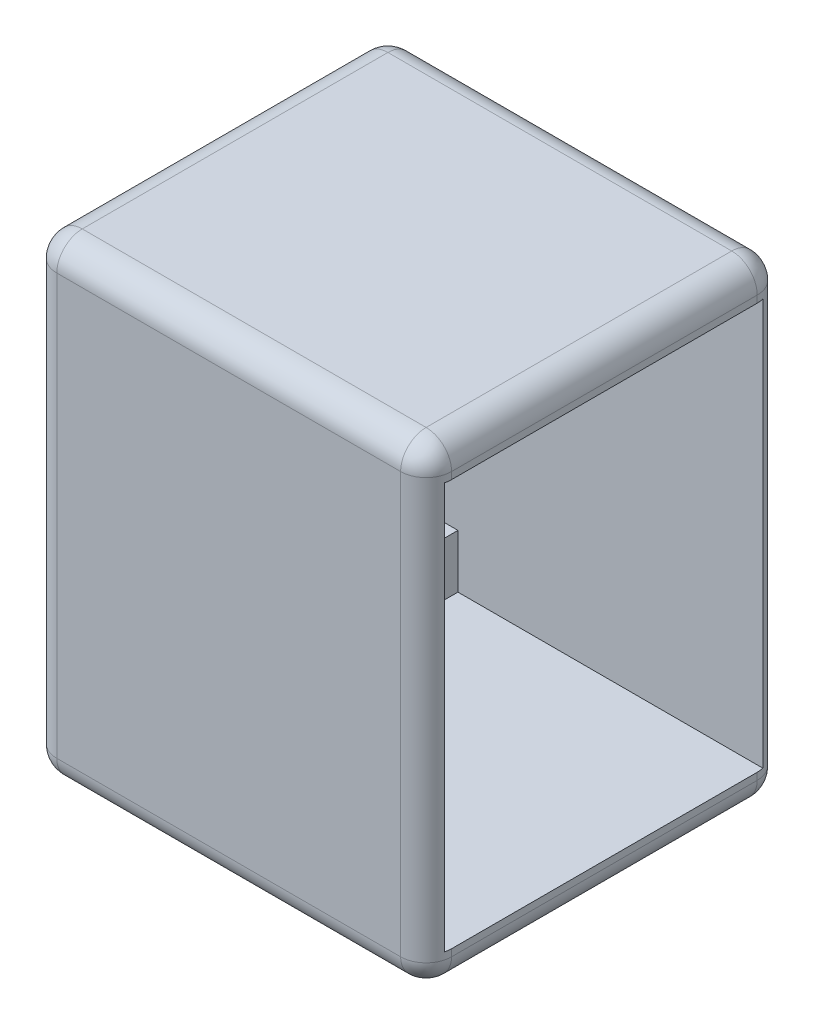
SolidWorks part; units mm, degrees
material "PLA"
ref_plane "Front Plane" through (0, 0, 0) normal (1, 0, 0) x (0, 1, 0)
ref_plane "Top Plane" through (0, 0, 0) normal (0, 0, 1) x (0, 1, 0)
ref_plane "Right Plane" through (0, 0, 0) normal (0, 1, 0) x (-1, 0, 0)
sketch "Sketch1" plane through (0, 0, 0) normal (1, 0, 0) x (0, 1, 0)
  line L5 (-37, 14) -> (-30.25, 14) construction
  line L6 (-37, 28) -> (0, 28)
  line L11 (-37, 28) -> (-37, 0)
  line L12 (-37, 0) -> (0, 0)
  line L20 (0, 28) -> (0, 0)
  line L21 (-30.25, 26.5) -> (-6.75, 26.5)
  line L22 (-30.25, 26.5) -> (-30.25, 1.5)
  line L23 (-30.25, 1.5) -> (-6.75, 1.5)
  line L24 (-6.75, 26.5) -> (-6.75, 1.5)
  line L25 (-6.75, 14) -> (0, 14) construction
  line L26 (-18.5, 0) -> (-18.5, 1.5) construction
  line L27 (-18.5, 28) -> (-18.5, 26.5) construction
  line L29 (-34.45, 1.5) -> (-2.55, 1.5)
  line L30 (-34.45, 1.5) -> (-34.45, 26.5)
  line L31 (-34.45, 26.5) -> (-2.55, 26.5)
  line L32 (-2.55, 1.5) -> (-2.55, 26.5)
  dimension "D1" = 4.2
  dimension "D2" = 25
  dimension "D3" = 4.2
  dimension "D6" = 37
  dimension "D7" = 23.5
  dimension "D9" = 1.5
extrude "Boss-Extrude1" add sketch "Sketch1" along normal blind 26 contours L20 L6 L11 L12 L21 L24 L23 L22 region at (0, -18.5, 27.536)
extrude "Boss-Extrude2" add sketch "Sketch1<3>" along normal blind 2 contours L31 L30 L29 L22 | L29 L32 L31 L24 region at (0, -32.35, 14) region at (0, -4.65, 14)
sketch "Sketch1<3>" plane through (0, 0, 0) normal (1, 0, 0) x (0, 1, 0) same geometry as "Sketch1"
sketch "Sketch2" plane through (26, 0, 0) normal (1, 0, 0) x (0, 1, 0)
  line L1 (-37, 28) -> (0, 28)
  line L2 (-37, 28) -> (-37, 0)
  line L3 (-37, 0) -> (0, 0)
  line L4 (0, 28) -> (0, 0)
sketch "Sketch3" plane through (0, 0, 0) normal (-1, 0, 0) x (0, -1, 0)
  line L1 (0, 28) -> (37, 28)
  line L2 (0, 28) -> (0, 0)
  line L3 (0, 0) -> (37, 0)
  line L4 (37, 28) -> (37, 0)
  line L5 (2.55, 26.5) -> (34.45, 26.5)
  line L6 (2.55, 26.5) -> (2.55, 1.5)
  line L7 (2.55, 1.5) -> (34.45, 1.5)
  line L8 (34.45, 26.5) -> (34.45, 1.5)
extrude "Boss-Extrude4" add sketch "Sketch3" along normal blind 3.5
sketch "Sketch5" plane through (-3.5, 0, 0) normal (-1, 0, 0) x (0, -1, 0)
  line L0 (23.25, 20) -> (23.25, 8) construction
  line L1 (0, 28) -> (37, 28)
  line L2 (0, 28) -> (0, 0)
  line L3 (0, 0) -> (37, 0)
  line L4 (37, 28) -> (37, 0)
  line L5 (30.25, 26.5) -> (30.25, 1.5) construction
  line L6 (34.45, 26.5) -> (2.55, 26.5) construction
  circle A0 centre (23.25, 20) radius 5.2
  circle A1 centre (23.25, 8) radius 5.2
  dimension "D1" = 10.4
  dimension "D2" = 7
  dimension "D3" = 12
  dimension "D4" = 6.5
extrude "Boss-Extrude5" add sketch "Sketch5" along normal blind 1.5
sketch "Sketch11" plane through (0, -37, 0) normal (0, -1, 0) x (1, 0, 0)
  line L0 (2.375, 14) -> (17.375, 14) construction
  line L1 (17.375, 10.4) -> (2.375, 11.65)
  line L2 (17.375, 17.6) -> (2.375, 16.35)
  line L3 (-5, 14) -> (0.025, 14) construction
  line L4 (-5, 0) -> (-5, 28) construction
  line L5 (20.975, 14) -> (26, 14) construction
  line L6 (26, 28) -> (26, 0) construction
  line L7 (2.375, 16.35) -> (2.375, 28) construction
  line L8 (26, 28) -> (-5, 28) construction
  line L9 (2.375, 0) -> (2.375, 11.65) construction
  line L10 (26, 0) -> (-5, 0) construction
  circle A0 centre (2.375, 14) radius 2.35
  circle A1 centre (17.375, 14) radius 3.6
  circle A2 centre (2.375, 14) radius 0.15
  circle A3 centre (17.375, 14) radius 0.15
  dimension "D1" = 4.7
  dimension "D2" = 7.2
  dimension "D4" = 0.3
  dimension "D3" = 15
extrude "Cut-Extrude5" cut sketch "Sketch11" against normal blind 1.5 contours A1 L2 A0 L1 | A1 A3 | L1 A0 L2 A2 | A3 | A2 region at (17.0855, -37, 10.5263) region at (9.5724, -37, 14) region at (0.0915, -37, 14) region at (2.375, -37, 14) region at (17.375, -37, 14)
extrude "Cut-Extrude12" cut sketch "Sketch11<7>" against normal blind 2 contours A2 | A3 region at (2.375, -37, 14) region at (17.375, -37, 14)
sketch "Sketch11<7>" plane through (0, -37, 0) normal (0, -1, 0) x (1, 0, 0) same geometry as "Sketch11"
fillet "Fillet1" radius 2 12 edges at (26, 0, 14) (26, -37, 14) (10.5, -37, 0) (-5, -37, 14) (-5, 0, 14) (-5, -18.5, 0) (10.5, 0, 0) (26, -18.5, 0) (26, -18.5, 28) (10.5, 0, 28) (-5, -18.5, 28) (10.5, -37, 28)
